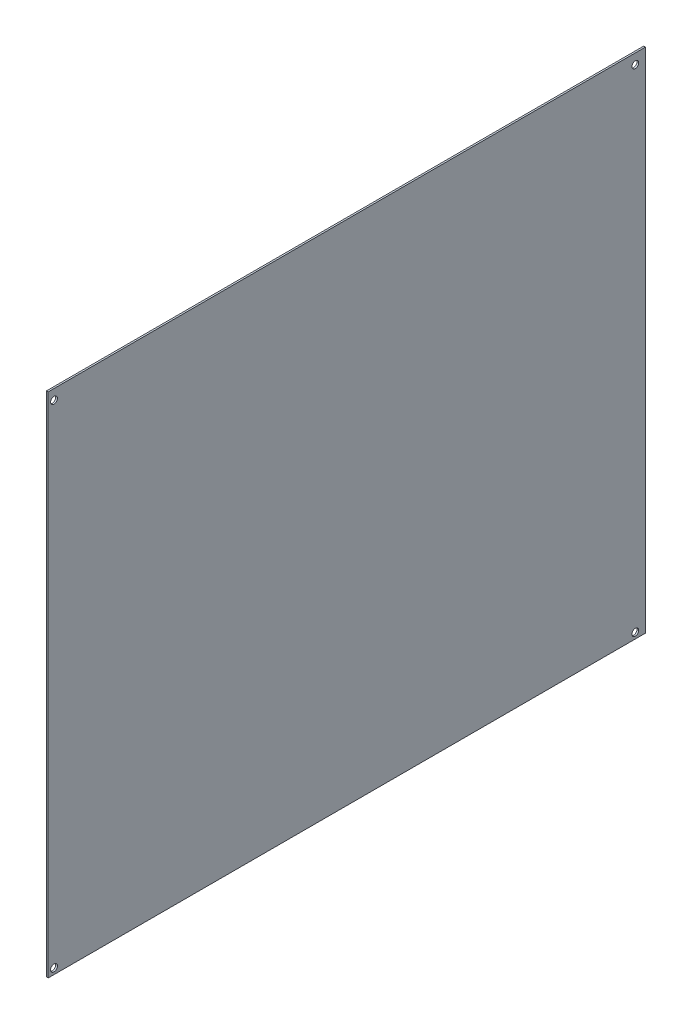
SolidWorks part; units mm, degrees
ref_plane "Front Plane" through (0, 0, 0) normal (0, 0, 1) x (1, 0, 0)
ref_plane "Top Plane" through (0, 0, 0) normal (0, 1, 0) x (1, 0, 0)
ref_plane "Right Plane" through (0, 0, 0) normal (1, 0, 0) x (0, 0, -1)
sketch "Sketch1" plane through (-873.1278, 0, 0) normal (-1, 0, 0) x (0, 0, 1)
  line L0 (-598.3652, 458.4348) -> (-598.3652, 509.8698) construction
  line L1 (-598.3652, 514.7974) -> (-38.0999, 514.7974) construction
  line L2 (-598.3652, 514.7974) -> (-598.3652, 38.0999) construction
  line L3 (-598.3652, 38.0999) -> (-38.0999, 38.0999) construction
  line L4 (-38.0999, 514.7974) -> (-38.0999, 38.0999) construction
  line L5 (-542.0026, 514.7974) -> (-593.4376, 514.7974) construction
  line L8 (-596.3652, 512.7974) -> (-40.0999, 512.7974)
  line L9 (-40.0999, 512.7974) -> (-40.0999, 40.0999)
  line L10 (-596.3652, 40.0999) -> (-40.0999, 40.0999)
  line L11 (-596.3652, 512.7974) -> (-596.3652, 40.0999)
  line L12 (-594.3, 38.0999) -> (-38.1, 38.0999) construction
  line L13 (-38.0999, -50) -> (-38.0999, 546.2) construction
  circle A0 centre (-586.859, 503.2912) radius 3.175 construction
  circle A1 centre (-45.541, 503.2912) radius 3.175 construction
  circle A2 centre (-45.541, 45.541) radius 3.175 construction
  circle A3 centre (-586.859, 45.541) radius 3.175 construction
  circle A4 centre (-586.859, 503.2912) radius 3.175
  circle A5 centre (-45.541, 503.2912) radius 3.175
  circle A6 centre (-45.541, 45.541) radius 3.175
  circle A7 centre (-586.859, 45.541) radius 3.175
  dimension "\"Panel_Offset\"" = 2
extrude "Boss-Extrude1" add sketch "Sketch1" along normal blind 1.6002
